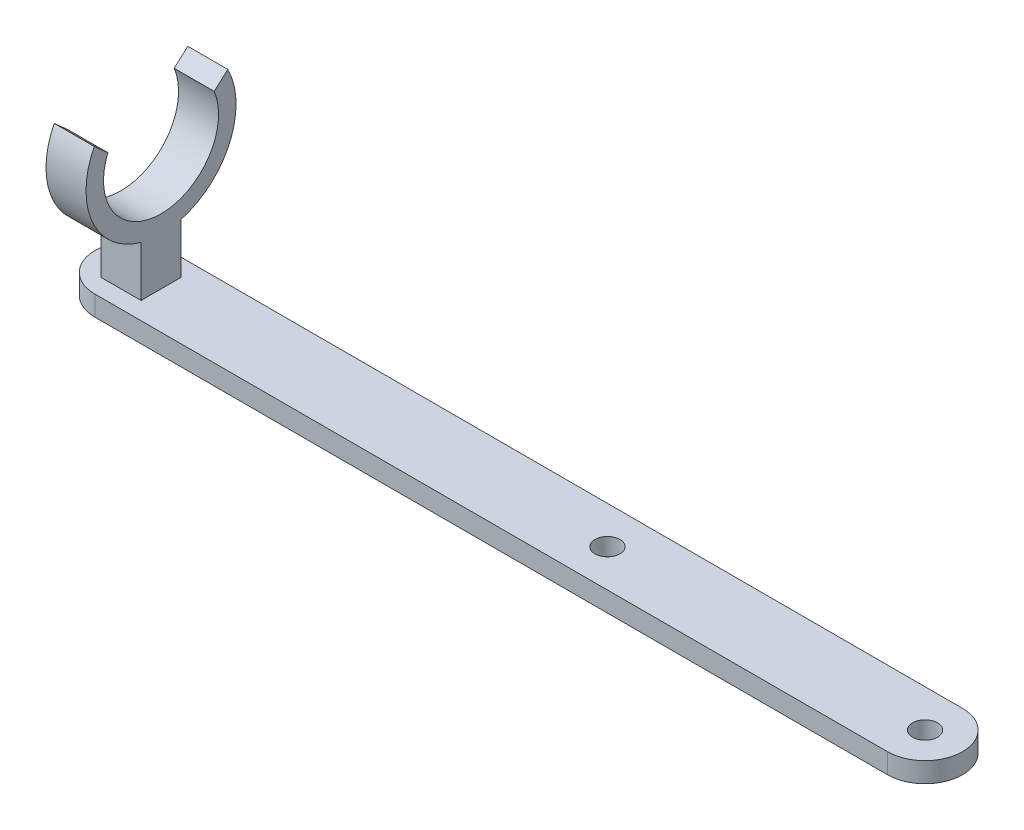
SolidWorks part; units mm, degrees
ref_plane "Front Plane" through (0, 0, 0) normal (0, 0, 1) x (1, 0, 0)
ref_plane "Top Plane" through (0, 0, 0) normal (0, 1, 0) x (1, 0, 0)
ref_plane "Right Plane" through (0, 0, 0) normal (1, 0, 0) x (0, 0, -1)
ref_axis "X Axis" through (-39.3295, 0, 0) along (1, 0, 0)
ref_axis "Y Axis" through (0, 0, -37.7472) along (0, 0, 1)
ref_axis "Z Axis" through (0, 35.6627, 0) along (0, -1, 0)
sketch "Sketch2" plane through (0, 0, 0) normal (0, 1, 0) x (1, 0, 0)
  line L0 (-31.75, 0) -> (31.75, 0) construction
  line L1 (-30, 0) -> (30, 0) construction
  line L4 (-31.75, 0) -> (-126.75, 0) construction
  line L5 (-126.75, 0) -> (31.75, 0) construction
  line L6 (-126.75, 7.5) -> (31.75, 7.5)
  line L7 (-126.75, -7.5) -> (31.75, -7.5)
  circle A0 centre (-31.75, 0) radius 2.5
  circle A1 centre (31.75, 0) radius 2.5
  arc A4 (-126.75, 7.5) -> (-126.75, -7.5) centre (-126.75, 0) ccw
  arc A5 (31.75, -7.5) -> (31.75, 7.5) centre (31.75, 0) ccw
  point P2 (0, 0)
  point P8 (0, 0)
  point P9 (-47.5, 0)
  dimension "D2" = 5
  dimension "D4" = 15
  dimension "D1" = 63.5
  dimension "D3" = 95
extrude "Boss-Extrude1" add sketch "Sketch2" along normal blind 4
ref_plane "Plane1" through (-125, 0, 0) normal (1, 0, 0) x (0, 0, -1)
sketch "Sketch3" plane through (-125, 0, 0) normal (1, 0, 0) x (0, 0, -1)
  line L0 (0, 0) -> (0, 28.5) construction
  line L1 (-13.3507, 35.338) -> (-10.6246, 32.9009)
  line L3 (10.6246, 32.9009) -> (13.3507, 35.338)
  arc A0 (10.6246, 32.9009) -> (-10.6246, 32.9009) centre (0, 28.5) cw
  arc A2 (-13.3507, 35.338) -> (13.3507, 35.338) centre (0, 28.5) ccw
  point P7 (0, 13.5)
  dimension "D2" = 11.5
  dimension "D3" = 3.5
  dimension "D1" = 28.5
extrude "Boss-Extrude2" add sketch "Sketch3" along normal blind 4 and the other way blind 4 separate body
sketch "Sketch4" plane through (0, 4, 0) normal (0, 1, 0) x (1, 0, 0)
  line L1 (-129, -4) -> (-121, -4)
  line L2 (-129, -4) -> (-129, 4)
  line L3 (-129, 4) -> (-121, 4)
  line L4 (-121, -4) -> (-121, 4)
  line L6 (-31.75, 0) -> (-121, 0) construction
  line L7 (-129, 11.5) -> (-129, -11.5) construction
  line L8 (-121, -11.5) -> (-121, 11.5) construction
  dimension "D1" = 8
extrude "Boss-Extrude3" add sketch "Sketch4" along normal up to surface (10.0432 mm away) up to face at (-125, 24.419, 0)
sketch "Sketch5" plane through (0, 0, 0) normal (0, -1, 0) x (1, 0, 0)
  circle A0 centre (-31.75, 0) radius 5.4
  circle A1 centre (31.75, 0) radius 5.4
  dimension "D1" = 10.8
extrude "Cut-Extrude1" cut sketch "Sketch5" against normal blind 0.5
sketch3d "3DSketch1"
  line L0 (-134.25, 0, 0) -> (39.25, 0, 0) construction
  arc A0 (-126.75, 0, -7.5) -> (-126.75, 0, 7.5) centre (-126.75, 0, 0) ccw construction
  arc A1 (31.75, 0, 7.5) -> (31.75, 0, -7.5) centre (31.75, 0, 0) ccw construction
  point P5 (-126.75, 7.5, 0)
  point P9 (31.75, 7.5, 0)
